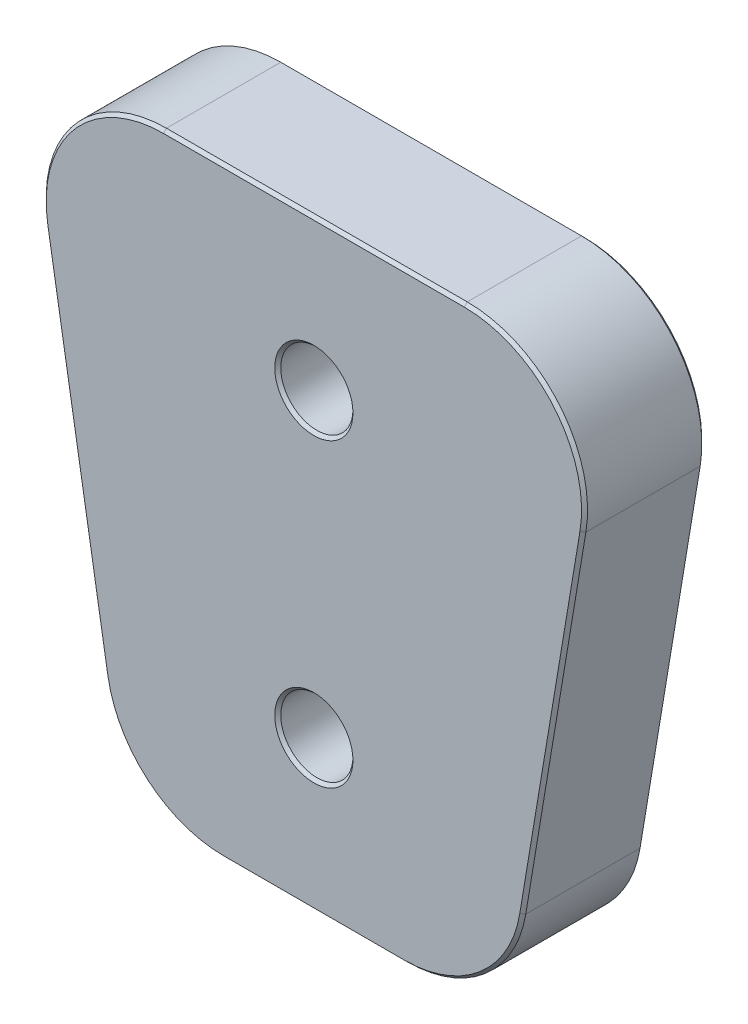
SolidWorks part; units mm, degrees
ref_plane "Front Plane" through (0, 0, 0) normal (0, 0, 1) x (1, 0, 0)
ref_plane "Top Plane" through (0, 0, 0) normal (0, 1, 0) x (1, 0, 0)
ref_plane "Right Plane" through (0, 0, 0) normal (1, 0, 0) x (0, 0, -1)
sketch "Sketch3" plane through (0, 0, 0) normal (0, 0, 1) x (1, 0, 0)
  line L0 (-6.3553, -23.288) -> (3.6447, -83.288)
  line L1 (13.3726, 0) -> (63.3726, 0)
  line L5 (23.3726, -100) -> (53.3726, -100)
  line L6 (73.1005, -83.288) -> (83.1005, -23.288)
  line L7 (38.3726, 0) -> (38.3726, -173.3588) construction
  arc A0 (63.3726, 0) -> (83.1005, -23.288) centre (63.3726, -20) cw
  arc A1 (13.3726, 0) -> (-6.3553, -23.288) centre (13.3726, -20) ccw
  arc A2 (53.3726, -100) -> (73.1005, -83.288) centre (53.3726, -80) ccw
  arc A3 (3.6447, -83.288) -> (23.3726, -100) centre (23.3726, -80) ccw
  point P7 (120, 0)
  point P10 (0, 0)
  point P13 (38.3726, -100)
  point P18 (0, 0)
  point P19 (0, 0)
  point P20 (0, 0)
  point P21 (116.6764, -23.6097)
  point P22 (0, 0)
  point P23 (5.9947, -83.9171)
  point P24 (0, 0)
  point P25 (0, 0)
  point P26 (13.3189, 0)
  point P27 (0, 0)
  point P28 (14.5409, 0)
  point P29 (82.3179, 0)
  point P30 (0, 0)
  point P31 (0, 0)
  point P32 (0, 0)
  point P33 (118.6736, -24.6143)
  point P34 (94.4088, -100)
  point P35 (0, 0)
  point P36 (0, 0)
  point P37 (92.3901, -100)
  point P38 (88.1005, -83.288)
  dimension "D3" = 20
  dimension "D5" = 20
  dimension "D6" = 30
  dimension "D1" = 50
  dimension "D2" = 100
  dimension "D4" = 0
extrude "Boss-Extrude1" add sketch "Sketch3" along normal blind 20 contours A3 L5 A2 L6 A0 L1 A1 L0
sketch "Sketch4" plane through (0, 0, 20) normal (0, 0, 1) x (1, 0, 0)
  line L0 (38.3726, 0) -> (38.3726, -50) construction
  line L1 (13.3726, 0) -> (63.3726, 0) construction
  line L2 (23.3726, -100) -> (53.3726, -100) construction
  line L3 (38.3726, 0) -> (38.3726, -50) construction
  line L4 (38.3726, -50) -> (38.3726, -100) construction
  line L5 (38.3726, -50) -> (38.3726, -100) construction
  circle A1 centre (38.3726, -25) radius 6
  circle A2 centre (38.3726, -75) radius 6
  point P7 (45.8726, -24.4466)
  point P13 (45.8726, -78.9777)
  dimension "D1" = 12
  dimension "D3" = 12
  dimension "D2" = 25
  dimension "D4" = 25
extrude "Cut-Extrude1" cut sketch "Sketch4" against normal blind 12
sketch "Sketch5" plane through (0, 0, 8) normal (0, 0, 1) x (1, 0, 0)
  circle A0 centre (38.3726, -25) radius 3.2
  circle A2 centre (38.3726, -75) radius 3.2
  dimension "D1" = 6.4
  dimension "D3" = 6.4
extrude "Cut-Extrude2" cut sketch "Sketch5" against normal through all
chamfer "Chamfer1" distance 0.5 angle 45 20 edges at (10.4451, -95.2604, 0) (38.3726, -100, 0) (66.3001, -95.2604, 0) (78.1005, -53.288, 0) (78.633, -7.0725, 0) (38.3726, 0, 0) (-1.8878, -7.0725, 0) (-1.3553, -53.288, 0) (41.5726, -75, 0) (41.5726, -25, 0) (-1.8878, -7.0725, 20) (38.3726, 0, 20) (78.633, -7.0725, 20) (78.1005, -53.288, 20) (66.3001, -95.2604, 20) (38.3726, -100, 20) (10.4451, -95.2604, 20) (-1.3553, -53.288, 20) (44.3726, -25, 20) (44.3726, -75, 20)
equation "\"D3@Sketch4\"= \"D1@Sketch4\""
equation "\"D3@Sketch5\"=\"D1@Sketch5\""
